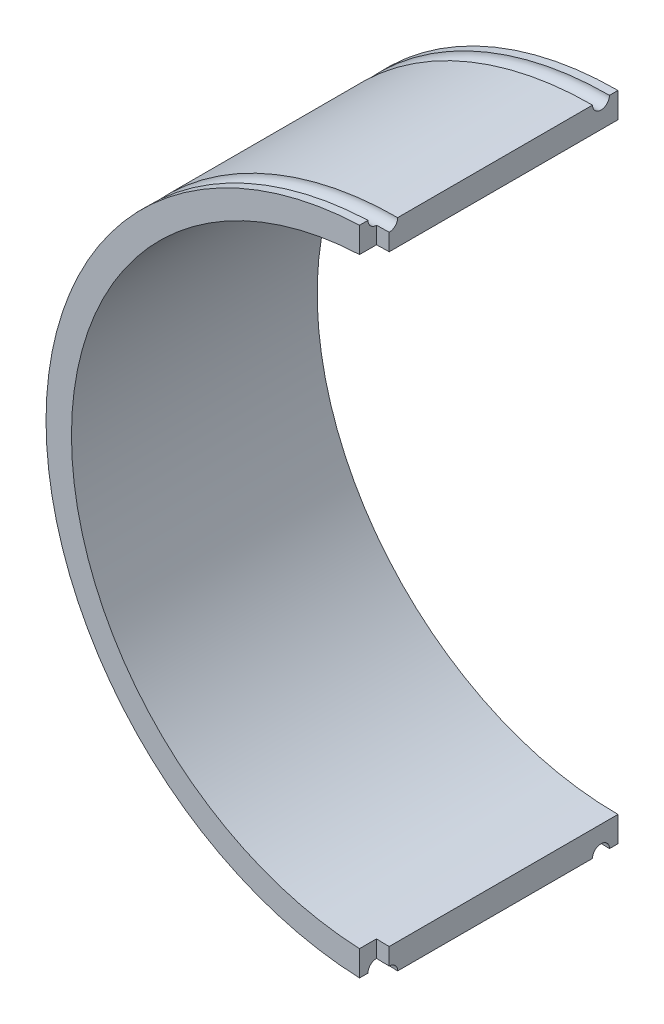
SolidWorks part; units mm, degrees
material "ABS"
ref_plane "Front Plane" through (0, 0, 0) normal (0, 0, 1) x (1, 0, 0)
ref_plane "Top Plane" through (0, 0, 0) normal (0, 1, 0) x (1, 0, 0)
ref_plane "Right Plane" through (0, 0, 0) normal (1, 0, 0) x (0, 0, -1)
sketch "Sketch1" plane through (0, 0, 0) normal (0, 0, 1) x (1, 0, 0)
  line L0 (0, 38.5) -> (0, 35.5)
  line L1 (0, -35.5) -> (0, -38.5)
  arc A0 (0, 35.5) -> (0, -35.5) centre (0, 0) ccw
  arc A1 (0, 38.5) -> (0, -38.5) centre (0, 0) ccw
  dimension "D1" = 3
  dimension "D2" = 77
extrude "Main Shell" add sketch "Sketch1" along normal blind 29
sketch "Sketch3" plane through (0, 0, 0) normal (1, 0, 0) x (0, 0, -1)
  line L0 (-29, 38.5) -> (0, 38.5) construction
  line L1 (-28, 38.5) -> (-26, 38.5)
  line L2 (-3, 38.5) -> (-1, 38.5)
  arc A0 (-28, 38.5) -> (-26, 38.5) centre (-27, 38.5) ccw
  arc A1 (-3, 38.5) -> (-1, 38.5) centre (-2, 38.5) ccw
  dimension "D1" = 2
  dimension "D2" = 2
  dimension "D3" = 2
revolve "Rubber Band Holder" cut sketch "Sketch3" angle 360 about axis through (0, 0, 29) along (0, 0, -1)
sketch "Sketch4" plane through (0, 0, 29) normal (0, 0, 1) x (1, 0, 0)
  line L0 (0, 38.5) -> (0, 35.5)
  line L1 (-1.5, 38.4708) -> (-1.5, 35.4683)
  line L2 (-1.5, -38.4708) -> (-1.5, -35.4683)
  line L3 (0, -38.5) -> (0, -35.5)
  line L4 (0, 0) -> (-38.5, 0) construction
  arc A0 (0, 35.5) -> (0, -35.5) centre (0, 0) ccw construction
  arc A1 (0, 35.5) -> (-1.5, 35.4683) centre (0, 0) ccw
  arc A2 (0, 38.5) -> (0, -38.5) centre (0, 0) ccw construction
  arc A3 (0, 38.5) -> (-1.5, 38.4708) centre (0, 0) ccw
  arc A4 (0, -38.5) -> (-1.5, -38.4708) centre (0, 0) cw
  arc A5 (0, -35.5) -> (-1.5, -35.4683) centre (0, 0) cw
  arc M1 (0, 38.5) -> (0, -38.5) centre (0, 0) ccw
  line M2 (0, -38.5) -> (0, -35.5)
  arc M3 (0, -35.5) -> (0, 35.5) centre (0, 0) cw
  line M4 (0, 35.5) -> (0, 38.5)
  dimension "D1" = 1.5
extrude "End Stop" cut sketch "Sketch4" against normal blind 2 contours A1 M4 M3 | M1 M2 M3 region at (-0.7501, 36.9898, 29) region at (-0.7501, -36.9898, 29)
